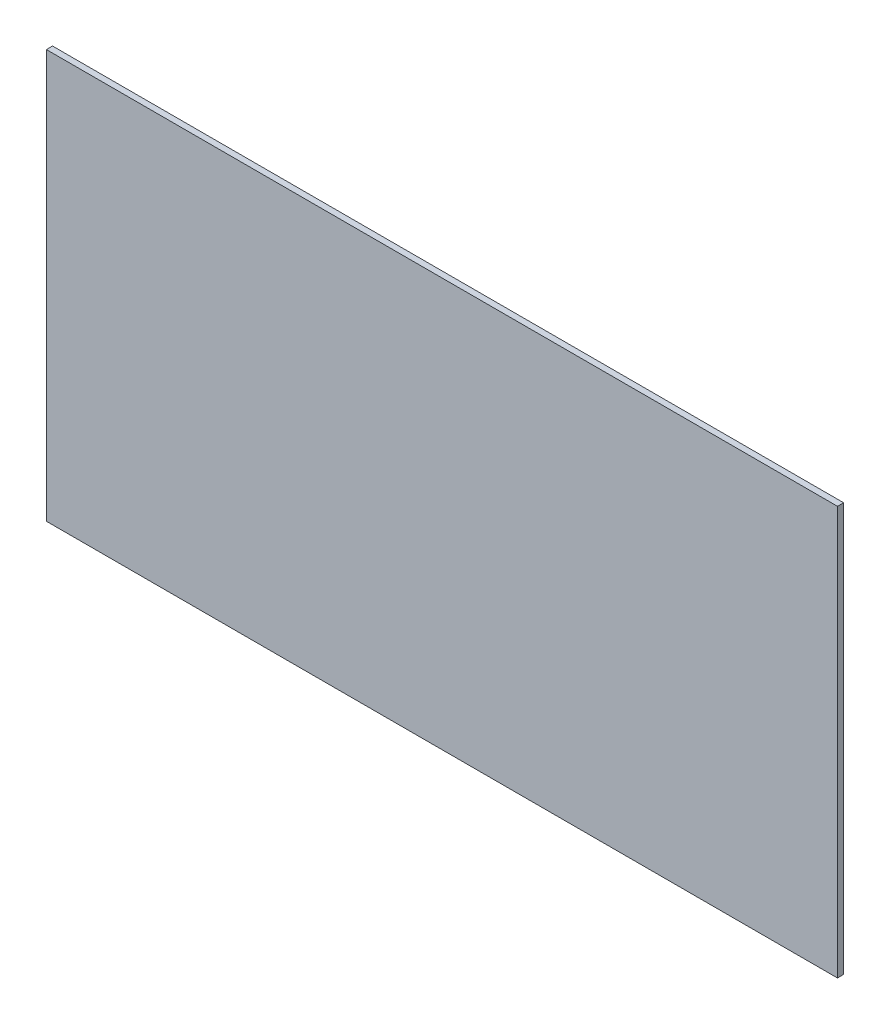
SolidWorks part; units mm, degrees
material "Acrylic (Medium-high impact)"
ref_plane "Front Plane" through (0, 0, 0) normal (0, 0, 1) x (1, 0, 0)
ref_plane "Top Plane" through (0, 0, 0) normal (0, 1, 0) x (1, 0, 0)
ref_plane "Right Plane" through (0, 0, 0) normal (1, 0, 0) x (0, 0, -1)
sketch "Sketch1" plane through (0, 0, 0) normal (0, 0, 1) x (1, 0, 0)
  line L1 (-289.5, -149.5) -> (289.5, -149.5)
  line L2 (-289.5, -149.5) -> (-289.5, 149.5)
  line L3 (-289.5, 149.5) -> (289.5, 149.5)
  line L4 (289.5, -149.5) -> (289.5, 149.5)
  line L5 (-289.5, -149.5) -> (289.5, 149.5) construction
  line L6 (-289.5, 149.5) -> (289.5, -149.5) construction
  point P0 (0, 0)
  dimension "D1" = 579
  dimension "D2" = 299
extrude "Boss-Extrude1" add sketch "Sketch1" along normal mid plane 4.4958
